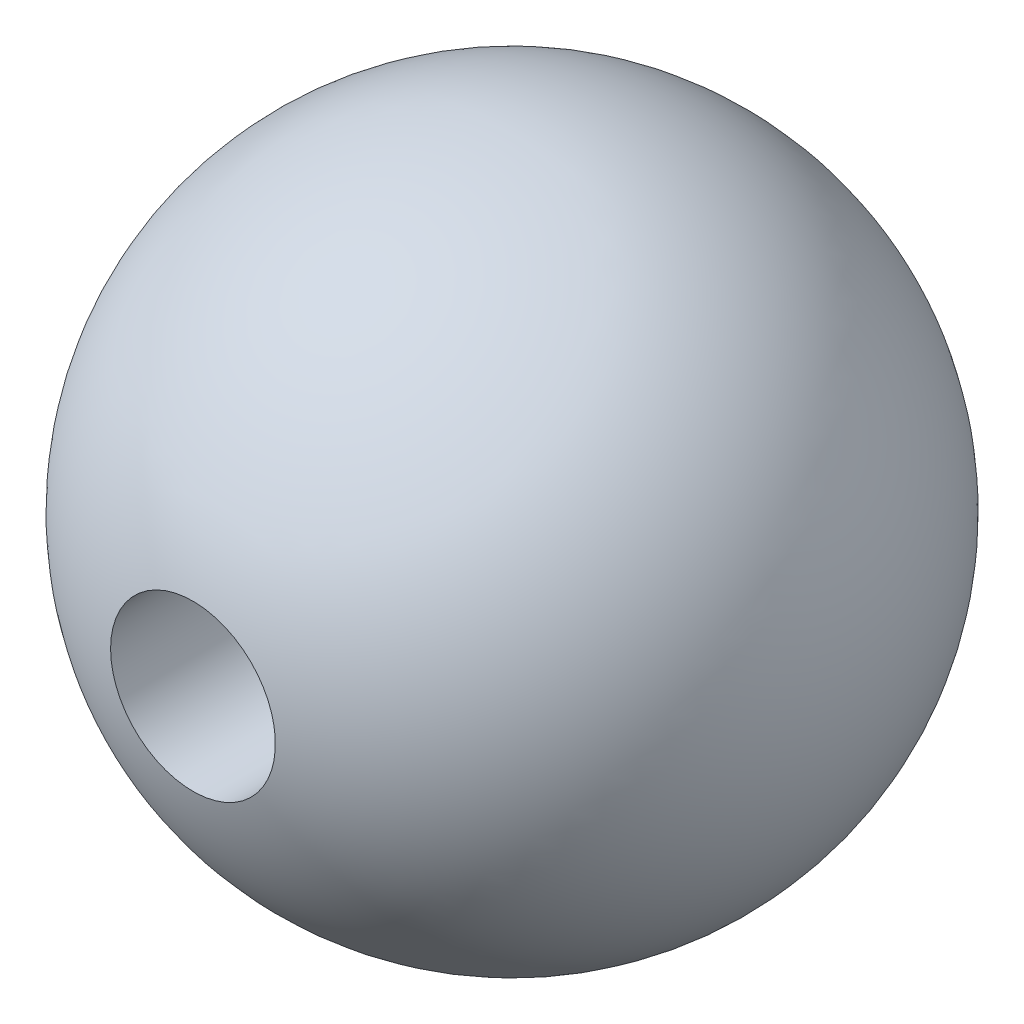
SolidWorks part; units mm, degrees
ref_plane "Front Plane" through (0, 0, 0) normal (0, 0, 1) x (1, 0, 0)
ref_plane "Top Plane" through (0, 0, 0) normal (0, 1, 0) x (1, 0, 0)
ref_plane "Right Plane" through (0, 0, 0) normal (1, 0, 0) x (0, 0, -1)
sketch "Sketch1" plane through (0, 0, 0) normal (0, 0, 1) x (1, 0, 0)
  line L0 (0, 0) -> (0, 12.7) construction
  line L1 (0, 12.7) -> (0, -12.7)
  arc A1 (0, 12.7) -> (0, -12.7) centre (0, 0) ccw
  dimension "D1" = 12.7
revolve "Revolve3" add sketch "Sketch1" angle 360 about L0
sketch "Sketch2" plane through (0, 0, 0) normal (0, 0, 1) x (1, 0, 0)
  circle A0 centre (0, 0) radius 3.175
  dimension "D1" = 6.35
extrude "Cut-Extrude1" cut sketch "Sketch2" against normal through all both and the other way through all
